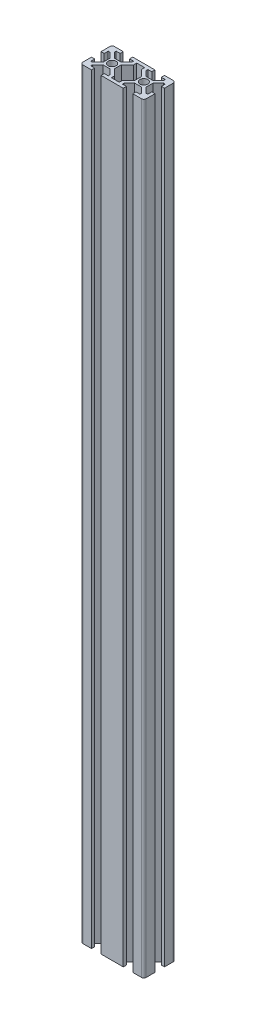
SolidWorks part; units mm, degrees
ref_plane "Front Plane" through (0, 0, 0) normal (0, 0, 1) x (1, 0, 0)
ref_plane "Top Plane" through (0, 0, 0) normal (0, 1, 0) x (1, 0, 0)
ref_plane "Right Plane" through (0, 0, 0) normal (1, 0, 0) x (0, 0, -1)
sketch "Sketch1" plane through (0, 0, 0) normal (0, 1, 0) x (1, 0, 0)
  line L0 (-10, 0) -> (10, 0) construction
  line L1 (0, 10) -> (0, -10) construction
  line L2 (-2.5, 8) -> (-2.5, 6.0858)
  line L3 (-2.5, 6.0858) -> (-6.4, 2.1858)
  line L4 (-6.4, 2.1858) -> (-6.4, -2.1858)
  line L5 (-2.5, -6.0858) -> (-6.4, -2.1858)
  line L6 (-2.5, -8) -> (-2.5, -6.0858)
  line L7 (-7, -10) -> (-7, -8)
  line L8 (7, 10) -> (7, 8)
  line L9 (7, 8) -> (4.5, 8)
  line L10 (4.5, 8) -> (4.5, 6.9142)
  line L11 (4.5, 6.9142) -> (7.8142, 3.6)
  line L12 (7.8142, 3.6) -> (12.1858, 3.6)
  line L13 (12.1858, 3.6) -> (15.5, 6.9142)
  line L14 (15.5, 6.9142) -> (15.5, 8)
  line L15 (15.5, 8) -> (13, 8)
  line L16 (13, 8) -> (13, 10)
  line L17 (13, 10) -> (18.5, 10)
  line L18 (10, 0) -> (10, 3.6) construction
  line L19 (-7, -8) -> (-4.5, -8)
  line L20 (2.5, 8) -> (2.5, 6.0858)
  line L21 (2.5, 6.0858) -> (6.4, 2.1858)
  line L22 (-4.5, -8) -> (-4.5, -6.9142)
  line L23 (-4.5, -6.9142) -> (-7.8142, -3.6)
  line L24 (-7.8142, -3.6) -> (-12.1858, -3.6)
  line L25 (6.4, 2.1858) -> (6.4, -2.1858)
  line L26 (-12.1858, -3.6) -> (-15.5, -6.9142)
  line L27 (20, 8.5) -> (20, 3)
  line L28 (20, 3) -> (18, 3)
  line L29 (18, 3) -> (18, 5.5)
  line L30 (18, 5.5) -> (16.9142, 5.5)
  line L31 (16.9142, 5.5) -> (13.6, 2.1858)
  line L32 (13.6, 2.1858) -> (13.6, -2.1858)
  line L33 (10, 0) -> (24.5324, 0) construction
  line L34 (15.5, 6.9142) -> (16.9142, 5.5) construction
  line L35 (-15.5, -6.9142) -> (-15.5, -8)
  line L36 (-15.5, -8) -> (-13, -8)
  line L37 (-13, -8) -> (-13, -10)
  line L38 (2.5, -8) -> (2.5, -6.0858)
  line L39 (2.5, -6.0858) -> (6.4, -2.1858)
  line L40 (16.9142, -5.5) -> (13.6, -2.1858)
  line L41 (18, -5.5) -> (16.9142, -5.5)
  line L42 (18, -3) -> (18, -5.5)
  line L43 (20, -3) -> (18, -3)
  line L44 (20, -8.5) -> (20, -3)
  line L45 (13, -10) -> (18.5, -10)
  line L46 (13, -8) -> (13, -10)
  line L47 (15.5, -8) -> (13, -8)
  line L48 (15.5, -6.9142) -> (15.5, -8)
  line L49 (12.1858, -3.6) -> (15.5, -6.9142)
  line L50 (7.8142, -3.6) -> (12.1858, -3.6)
  line L51 (4.5, -6.9142) -> (7.8142, -3.6)
  line L52 (4.5, -8) -> (4.5, -6.9142)
  line L53 (7, -8) -> (4.5, -8)
  line L54 (7, -10) -> (7, -8)
  line L55 (-13, -10) -> (-18.5, -10)
  line L56 (-20, -8.5) -> (-20, -3)
  line L57 (-20, -3) -> (-18, -3)
  line L58 (-18, -3) -> (-18, -5.5)
  line L59 (-18, -5.5) -> (-16.9142, -5.5)
  line L60 (-16.9142, -5.5) -> (-13.6, -2.1858)
  line L61 (-13.6, 2.1858) -> (-13.6, -2.1858)
  line L62 (-16.9142, 5.5) -> (-13.6, 2.1858)
  line L63 (2.5, -8) -> (-2.5, -8)
  line L64 (-18, 5.5) -> (-16.9142, 5.5)
  line L65 (-18, 3) -> (-18, 5.5)
  line L66 (-20, 3) -> (-18, 3)
  line L67 (-20, 8.5) -> (-20, 3)
  line L68 (-13, 10) -> (-18.5, 10)
  line L69 (2.5, 8) -> (-2.5, 8)
  line L70 (-13, 8) -> (-13, 10)
  line L71 (-15.5, 8) -> (-13, 8)
  line L72 (-15.5, 6.9142) -> (-15.5, 8)
  line L73 (-12.1858, 3.6) -> (-15.5, 6.9142)
  line L74 (-7.8142, 3.6) -> (-12.1858, 3.6)
  line L75 (-4.5, 6.9142) -> (-7.8142, 3.6)
  line L76 (-4.5, 8) -> (-4.5, 6.9142)
  line L77 (7, -10) -> (-7, -10)
  line L78 (-7, 8) -> (-4.5, 8)
  line L79 (-7, 10) -> (-7, 8)
  line L109 (7, 10) -> (-7, 10)
  circle A0 centre (-10, 0) radius 2.5
  circle A1 centre (10, 0) radius 2.5
  arc A2 (-18.5, -10) -> (-20, -8.5) centre (-18.5, -8.5) cw
  arc A3 (18.5, 10) -> (20, 8.5) centre (18.5, 8.5) cw
  arc A4 (18.5, -10) -> (20, -8.5) centre (18.5, -8.5) ccw
  arc A5 (-18.5, 10) -> (-20, 8.5) centre (-18.5, 8.5) ccw
  point P33 (0, 8)
  point P47 (0, -8)
  dimension "D3" = 10
  dimension "D13" = 1.5
  dimension "D2" = 5
  dimension "D4" = 2
  dimension "D5" = 20
  dimension "D6" = 6.4
  dimension "D8" = 6
  dimension "D9" = 11
  dimension "D10" = 2
  dimension "D11" = 2
  dimension "D14" = 3
  dimension "D15" = 2
extrude "Boss-Extrude1" add sketch "Sketch1" along normal mid plane 480
ref_axis "Axis1" through (10, 240, 0) along (0, -1, 0)
ref_axis "Axis2" through (-10, 240, 0) along (0, -1, 0)
